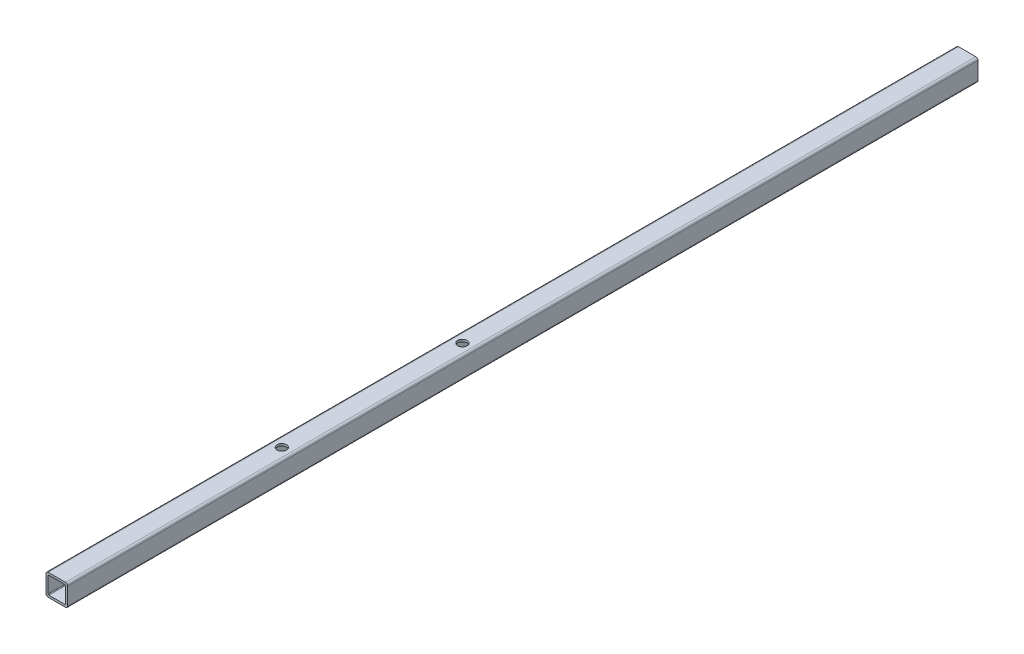
SolidWorks part; units mm, degrees
material "1.0553 (S355J0)"
ref_plane "Płaszczyzna przednia" through (0, 0, 0) normal (0, 0, 1) x (1, 0, 0)
ref_plane "Płaszczyzna górna" through (0, 0, 0) normal (0, 1, 0) x (1, 0, 0)
ref_plane "Płaszczyzna prawa" through (0, 0, 0) normal (1, 0, 0) x (0, 0, -1)
sketch "Szkic1" plane through (0, 0, 0) normal (0, 0, 1) x (1, 0, 0)
  line L0 (0, -55) -> (0, 55) construction
  line L1 (-12, -15) -> (12, -15)
  line L2 (-15, -12) -> (-15, 12)
  line L3 (-12, 15) -> (12, 15)
  line L4 (15, -12) -> (15, 12)
  line L5 (-11, -12) -> (11, -12)
  line L6 (-12, -11) -> (-12, 11)
  line L7 (-11, 12) -> (11, 12)
  line L8 (12, -11) -> (12, 11)
  line L10 (55, 0) -> (-55, 0) construction
  arc A0 (-12, -15) -> (-15, -12) centre (-12, -12) cw
  arc A1 (-15, 12) -> (-12, 15) centre (-12, 12) cw
  arc A2 (12, 15) -> (15, 12) centre (12, 12) cw
  arc A3 (15, -12) -> (12, -15) centre (12, -12) cw
  arc A4 (-12, -11) -> (-11, -12) centre (-11, -11) ccw
  arc A5 (11, -12) -> (12, -11) centre (11, -11) ccw
  arc A6 (12, 11) -> (11, 12) centre (11, 11) ccw
  arc A7 (-11, 12) -> (-12, 11) centre (-11, 11) ccw
  point P11 (0, 0)
  point P28 (0, -15)
  point P31 (-15, 0)
  dimension "D7" = 3
  dimension "D8" = 1
  dimension "D1" = 30
  dimension "D2" = 30
  dimension "D3" = 3
  dimension "D4" = 3
  dimension "D5" = 3
  dimension "D6" = 3
extrude "Dodanie-wyciągnięcie1" add sketch "Szkic1" along normal blind 1260
sketch "Szkic4" [suppressed] plane through (0, 0, 0) normal (1, 0, 0) x (0, 0, -1)
  line L0 (-119.2, 0) -> (0, 0) construction
  line L1 (-119.2, -12) -> (-119.2, 12) construction
  circle A0 centre (-59.6, 0) radius 5
  dimension "D1" = 10
extrude "Wytnij-wyciągnięcie3" [suppressed] cut sketch "Szkic4" along normal blind 29 and the other way blind 45
sketch "Szkic2" [suppressed] plane through (0, 0, 0) normal (1, 0, 0) x (0, 0, -1)
  line L4 (-1260, -15) -> (0, -15) construction
  line L6 (-1260, 15) -> (-1260, -15)
  line L7 (-1260, -15) -> (-420, -15)
  line L9 (-420, -15) -> (-402.6795, 15)
  line L10 (-1260, 15) -> (0, 15) construction
  line L11 (-402.6795, 15) -> (-1260, 15)
  line L12 (-17.3205, -15) -> (0, 15)
  line L14 (0, 15) -> (0, -15)
  line L15 (0, -15) -> (-17.3205, -15)
  dimension "D1" = 60
  dimension "D2" = 420
extrude "Wytnij-wyciągnięcie1" [suppressed] cut sketch "Szkic2" against normal blind 72 and the other way blind 88
sketch "Szkic3" [suppressed] plane through (0, 0, 0) normal (1, 0, 0) x (0, 0, -1)
  line L0 (-320, 15) -> (-320, -15) construction
  line L1 (-640, 15) -> (0, 15) construction
  line L2 (-640, -15) -> (0, -15) construction
  line L3 (-640, 0) -> (0, 0) construction
  line L4 (-640, -12) -> (-640, 12) construction
  circle A0 centre (-390, 0) radius 5
  circle A1 centre (-250, 0) radius 5
  dimension "D2" = 10
  dimension "D1" = 140
extrude "Wytnij-wyciągnięcie2" [suppressed] cut sketch "Szkic3" along normal blind 42 and the other way blind 37
sketch "Szkic5" [suppressed] plane through (-15, 0, 0) normal (-1, 0, 0) x (0, 0, 1)
  line L1 (185, 12) -> (185, -12) construction
  circle A0 centre (20, 0) radius 6.25
  circle A1 centre (140, 0) radius 6.25
  dimension "D3" = 12.5
  dimension "D1" = 120
  dimension "D4" = 45
extrude "Wytnij-wyciągnięcie4" [suppressed] cut sketch "Szkic5" against normal up to surface (30 mm away)
sketch "Szkic6" plane through (0, 15, 0) normal (0, 1, 0) x (1, 0, 0)
  line L0 (12, -1260) -> (-12, -1260) construction
  line L1 (0, -16.5) -> (0, 16.5) construction
  circle A0 centre (0, -948.6) radius 6.5
  circle A1 centre (0, -698.6) radius 6.5
  dimension "D3" = 13
  dimension "D1" = 311.4
  dimension "D2" = 250
extrude "Wytnij-wyciągnięcie5" cut sketch "Szkic6" against normal up to surface (30 mm away) up to face at (0, -15, 630)
